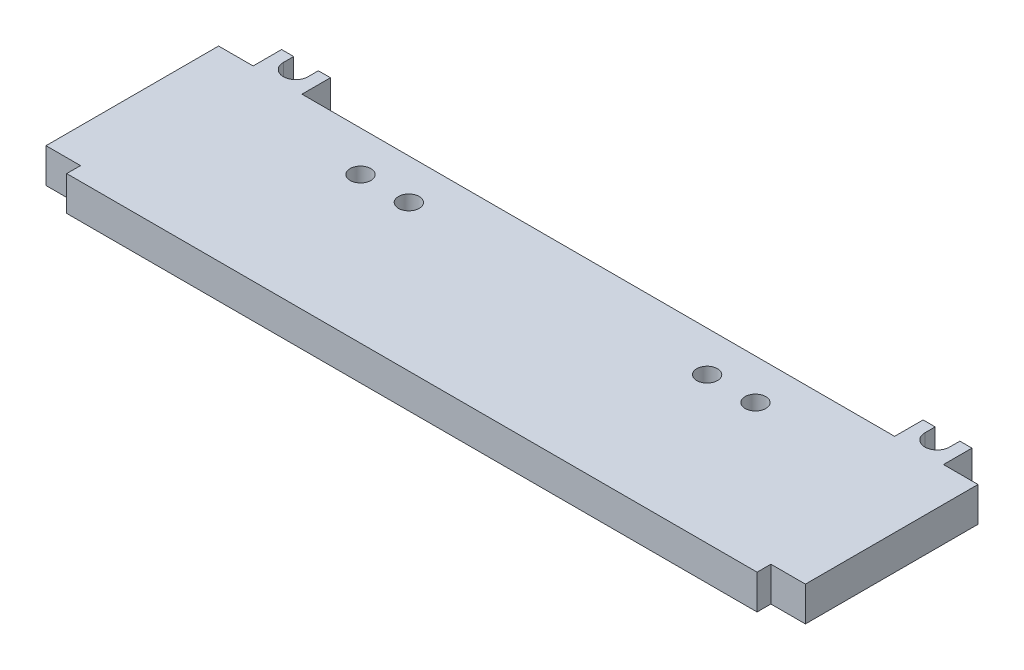
SolidWorks part; units mm, degrees
ref_plane "Front Plane" through (0, 0, 0) normal (0, 0, 1) x (1, 0, 0)
ref_plane "Top Plane" through (0, 0, 0) normal (0, 1, 0) x (1, 0, 0)
ref_plane "Right Plane" through (0, 0, 0) normal (1, 0, 0) x (0, 0, -1)
sketch "Sketch1" plane through (0, 0, 0) normal (1, 0, 0) x (0, 0, -1)
  line L1 (-17.1369, 5.602) -> (9.8631, 5.602)
  line L2 (-17.1369, 5.602) -> (-17.1369, 0.602)
  line L3 (-17.1369, 0.602) -> (9.8631, 0.602)
  line L4 (9.8631, 5.602) -> (9.8631, 0.602)
  dimension "D1" = 27
  dimension "D2" = 5
extrude "Boss-Extrude1" add sketch "Sketch1" along normal blind 110
sketch "Sketch2" plane through (0, 0.602, 0) normal (0, -1, 0) x (1, 0, 0)
  line L1 (0, -9.8631) -> (5, -9.8631)
  line L2 (0, -9.8631) -> (0, -7.3631)
  line L3 (0, -7.3631) -> (5, -7.3631)
  line L4 (5, -9.8631) -> (5, -7.3631)
  dimension "D1" = 5
  dimension "D2" = 2.5
sketch "Sketch5" plane through (0, 0, 0) normal (-1, 0, 0) x (0, 0, 1)
  line L0 (0, 0.602) -> (0, 5.602) construction
  line L1 (17.1369, 0.602) -> (-9.8631, 0.602) construction
  line L2 (-9.8631, 5.602) -> (17.1369, 5.602) construction
sketch "Sketch6" plane through (0, 5.602, 0) normal (0, 1, 0) x (1, 0, 0)
  line L1 (0, -17.1369) -> (5, -17.1369)
  line L2 (0, -17.1369) -> (0, -15.1369)
  line L3 (0, -15.1369) -> (5, -15.1369)
  line L4 (5, -17.1369) -> (5, -15.1369)
  dimension "D1" = 5
  dimension "D2" = 2
sketch "Sketch7" plane through (0, 5.602, 0) normal (0, 1, 0) x (1, 0, 0)
  line L0 (110, -3.6369) -> (0, 0) construction
  line L1 (110, 9.8631) -> (110, -17.1369) construction
  line L2 (55, -1.8184) -> (55, -17.1369) construction
  line L3 (110, -17.1369) -> (0, -17.1369) construction
sketch "Sketch8" plane through (0, 0, 17.1369) normal (0, 0, 1) x (1, 0, 0)
  line L0 (55, 5.602) -> (55, 0.602) construction
  line L1 (110, 0.602) -> (0, 0.602) construction
ref_plane "Plane3" through (55, 0, 0) normal (1, 0, 0) x (0, 0, -1)
sketch "Sketch13" plane through (0, 5.602, 0) normal (0, 1, 0) x (1, 0, 0)
  line L0 (55, -1.8184) -> (4.7941, -1.8184) construction
  line L1 (29.897, -1.8184) -> (29.897, 9.8631) construction
  line L2 (110, 9.8631) -> (0, 9.8631) construction
  line L3 (29.897, 4.0223) -> (26.397, 4.0223) construction
  line L4 (17.3455, 4.0223) -> (17.3455, 9.8631) construction
  line L5 (29.897, 4.0223) -> (33.397, 4.0223) construction
  dimension "D1" = 3.5
  dimension "D2" = 3.5
hole_wizard "M3 Tapped Hole1" positions "3DSketch2" profile "Sketch14" tap size "M3" standard "ISO"
sketch3d "3DSketch2"
  point P0 (26.397, 5.602, -4.0223)
  point P3 (33.397, 5.602, -4.0223)
sketch "Sketch14" plane through (26.397, 5.602, -4.0223) normal (1, 0, 0) x (0, 0, 1)
  line L0 (0, 0) -> (0, 8.2511)
  line L1 (0, 8.2511) -> (1.25, 7.5)
  line L2 (1.25, 7.5) -> (1.25, 6)
  line L3 (1.25, 6) -> (1.5, 6)
  line L4 (1.5, 6) -> (1.5, 0)
  line L5 (1.5, 0) -> (0, 0)
  line L10 (0, 8.2511) -> (-1.25, 7.5) construction
  line L11 (0, -6.35) -> (0, 107.95) construction
  dimension "Tap Drill Dia." = 2.5
  dimension "Tap Drill Depth" = 7.5
  dimension "Thread Major Dia." = 3
  dimension "Thread Depth" = 6
  dimension "Drill Angle" = 118
ref_plane "Plane4" through (55, 0, 0) normal (1, 0, 0) x (0, 0, -1)
mirror "Mirror3" about plane through (55, 0, 0) normal (1, 0, 0) of "M3 Tapped Hole1"
extrude "Cut-Extrude1" cut sketch "Sketch6" against normal blind 10 contours L4 L3 L2 L1
mirror "Mirror4" about plane through (55, 0, 0) normal (1, 0, 0) of "Cut-Extrude1"
sketch "Sketch17" plane through (0, 5.602, 0) normal (0, 1, 0) x (1, 0, 0)
  line L0 (110, 9.8631) -> (105, 9.8631) construction
  line L1 (110, 9.8631) -> (0, 9.8631) construction
  line L2 (105, 9.8631) -> (105, 13.9871)
  line L3 (103.25, 12.4943) -> (103.25, 13.9871)
  line L4 (105, 13.9871) -> (103.25, 13.9871)
  line L5 (105, 9.8631) -> (97.924, 9.8631)
  line L7 (99.674, 12.4943) -> (99.674, 13.9871)
  line L8 (99.674, 13.9871) -> (97.924, 13.9871)
  line L9 (97.924, 13.9871) -> (97.924, 9.8631)
  arc A0 (103.25, 12.4943) -> (99.674, 12.4943) centre (101.462, 12.4943) cw
  dimension "D1" = 5
  dimension "D2" = 1.75
  dimension "D3" = 1.75
extrude "Boss-Extrude2" add sketch "Sketch17" against normal blind 5
sketch "Sketch18" plane through (0, 5.602, 0) normal (0, 1, 0) x (1, 0, 0)
  line L0 (55, -17.1369) -> (55, 9.8631) construction
  line L1 (97.924, 9.8631) -> (0, 9.8631) construction
sketch "Sketch19" plane through (0, 0, -9.8631) normal (0, 0, -1) x (-1, 0, 0)
  line L0 (-55, 5.602) -> (-55, 0.602) construction
  line L1 (-97.924, 0.602) -> (0, 0.602) construction
ref_plane "Plane5" through (55, 0, 0) normal (-1, 0, 0) x (0, 0, 1)
mirror "Mirror5" about plane through (55, 0, 0) normal (-1, 0, 0) of "Boss-Extrude2"
